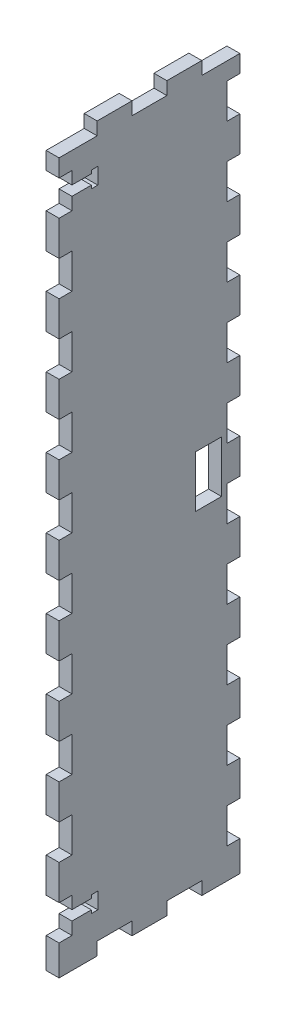
SolidWorks part; units mm, degrees
ref_plane "Front Plane" through (0, 0, 0) normal (0, 0, 1) x (1, 0, 0)
ref_plane "Top Plane" through (0, 0, 0) normal (0, 1, 0) x (1, 0, 0)
ref_plane "Right Plane" through (0, 0, 0) normal (1, 0, 0) x (0, 0, -1)
sketch "Sketch1" plane through (0, 0, 0) normal (1, 0, 0) x (0, 0, -1)
  line L0 (6.35, 355.6) -> (6.35, 349.25) construction
  line L1 (0, 0) -> (88.9, 0) construction
  line L2 (0, 0) -> (0, 6.35) construction
  line L3 (6.35, 355.6) -> (76.2, 355.6) construction
  line L4 (88.9, 0) -> (88.9, 6.35) construction
  line L5 (0, 6.35) -> (88.9, 6.35) construction
  line L6 (6.35, 349.25) -> (88.9, 349.25) construction
  line L7 (82.55, 355.6) -> (82.55, 338.1375) construction
  line L8 (0, 6.35) -> (0, 0)
  line L9 (0, 0) -> (6.35, 0)
  line L10 (6.35, 0) -> (18.7325, 0)
  line L11 (18.7325, 0) -> (18.7325, 6.35)
  line L12 (18.7325, 6.35) -> (35.8775, 6.35)
  line L13 (35.8775, 6.35) -> (35.8775, 0)
  line L14 (35.8775, 0) -> (53.0225, 0)
  line L15 (53.0225, 0) -> (53.0225, 6.35)
  line L16 (53.0225, 6.35) -> (70.1675, 6.35)
  line L17 (70.1675, 6.35) -> (70.1675, 0)
  line L18 (70.1675, 0) -> (82.55, 0)
  line L19 (82.55, 0) -> (88.9, 0)
  line L20 (88.9, 0) -> (88.9, 6.35)
  line L21 (6.35, 12.3825) -> (6.35, 0) construction
  line L22 (0, 0) -> (0, 349.25) construction
  line L23 (0, 6.35) -> (0, 14.9225)
  line L24 (0, 49.2125) -> (6.35, 49.2125)
  line L25 (6.35, 49.2125) -> (6.35, 66.3575)
  line L26 (6.35, 66.3575) -> (0, 66.3575)
  line L27 (0, 66.3575) -> (0, 83.5025)
  line L28 (0, 83.5025) -> (6.35, 83.5025)
  line L29 (6.35, 83.5025) -> (6.35, 100.6475)
  line L30 (6.35, 100.6475) -> (0, 100.6475)
  line L31 (0, 100.6475) -> (0, 117.7925)
  line L32 (0, 117.7925) -> (6.35, 117.7925)
  line L33 (6.35, 117.7925) -> (6.35, 134.9375)
  line L34 (6.35, 134.9375) -> (0, 134.9375)
  line L35 (0, 134.9375) -> (0, 152.0825)
  line L36 (0, 152.0825) -> (6.35, 152.0825)
  line L37 (6.35, 152.0825) -> (6.35, 169.2275)
  line L38 (6.35, 169.2275) -> (0, 169.2275)
  line L39 (0, 169.2275) -> (0, 186.3725)
  line L40 (0, 186.3725) -> (6.35, 186.3725)
  line L41 (6.35, 186.3725) -> (6.35, 203.5175)
  line L42 (6.35, 203.5175) -> (0, 203.5175)
  line L43 (0, 203.5175) -> (0, 220.6625)
  line L44 (0, 220.6625) -> (6.35, 220.6625)
  line L45 (6.35, 220.6625) -> (6.35, 237.8075)
  line L46 (6.35, 237.8075) -> (0, 237.8075)
  line L47 (0, 237.8075) -> (0, 254.9525)
  line L48 (0, 254.9525) -> (6.35, 254.9525)
  line L49 (6.35, 254.9525) -> (6.35, 272.0975)
  line L50 (6.35, 272.0975) -> (0, 272.0975)
  line L51 (0, 272.0975) -> (0, 289.2425)
  line L52 (0, 289.2425) -> (6.35, 289.2425)
  line L53 (6.35, 289.2425) -> (6.35, 306.3875)
  line L54 (6.35, 306.3875) -> (0, 306.3875)
  line L55 (0, 306.3875) -> (0, 323.5325)
  line L56 (0, 323.5325) -> (6.35, 323.5325)
  line L57 (6.35, 323.5325) -> (6.35, 329.692)
  line L58 (6.35, 340.6775) -> (0, 340.6775)
  line L59 (0, 340.6775) -> (0, 349.25)
  line L60 (6.35, 349.25) -> (0, 349.25)
  line L61 (6.35, 334.518) -> (6.35, 340.6775)
  line L62 (6.35, 349.25) -> (18.7325, 349.25)
  line L63 (18.7325, 349.25) -> (18.7325, 355.6)
  line L64 (18.7325, 355.6) -> (35.8775, 355.6)
  line L65 (35.8775, 355.6) -> (35.8775, 349.25)
  line L66 (35.8775, 349.25) -> (53.0225, 349.25)
  line L67 (53.0225, 349.25) -> (53.0225, 355.6)
  line L68 (53.0225, 355.6) -> (70.1675, 355.6)
  line L69 (70.1675, 355.6) -> (70.1675, 349.25)
  line L70 (70.1675, 349.25) -> (88.9, 349.25)
  line L71 (88.9, 6.35) -> (88.9, 14.9225)
  line L72 (88.9, 14.9225) -> (82.55, 14.9225)
  line L73 (82.55, 12.3825) -> (82.55, 0) construction
  line L74 (82.55, 14.9225) -> (82.55, 32.0675)
  line L75 (82.55, 32.0675) -> (88.9, 32.0675)
  line L76 (88.9, 32.0675) -> (88.9, 49.2125)
  line L77 (88.9, 66.3575) -> (88.9, 83.5025)
  line L78 (82.55, 66.3575) -> (88.9, 66.3575)
  line L79 (82.55, 49.2125) -> (82.55, 66.3575)
  line L80 (88.9, 49.2125) -> (82.55, 49.2125)
  line L81 (88.9, 100.6475) -> (88.9, 117.7925)
  line L82 (82.55, 100.6475) -> (88.9, 100.6475)
  line L83 (82.55, 83.5025) -> (82.55, 100.6475)
  line L84 (88.9, 83.5025) -> (82.55, 83.5025)
  line L85 (88.9, 134.9375) -> (88.9, 152.0825)
  line L86 (82.55, 134.9375) -> (88.9, 134.9375)
  line L87 (82.55, 117.7925) -> (82.55, 134.9375)
  line L88 (88.9, 117.7925) -> (82.55, 117.7925)
  line L89 (88.9, 169.2275) -> (88.9, 186.3725)
  line L90 (82.55, 169.2275) -> (88.9, 169.2275)
  line L91 (82.55, 152.0825) -> (82.55, 169.2275)
  line L92 (88.9, 152.0825) -> (82.55, 152.0825)
  line L93 (88.9, 203.5175) -> (88.9, 220.6625)
  line L94 (82.55, 203.5175) -> (88.9, 203.5175)
  line L95 (82.55, 186.3725) -> (82.55, 203.5175)
  line L96 (88.9, 186.3725) -> (82.55, 186.3725)
  line L97 (88.9, 237.8075) -> (88.9, 254.9525)
  line L98 (82.55, 237.8075) -> (88.9, 237.8075)
  line L99 (82.55, 220.6625) -> (82.55, 237.8075)
  line L100 (88.9, 220.6625) -> (82.55, 220.6625)
  line L101 (88.9, 272.0975) -> (88.9, 289.2425)
  line L102 (82.55, 272.0975) -> (88.9, 272.0975)
  line L103 (82.55, 254.9525) -> (82.55, 272.0975)
  line L104 (88.9, 254.9525) -> (82.55, 254.9525)
  line L105 (88.9, 306.3875) -> (88.9, 323.5325)
  line L106 (82.55, 306.3875) -> (88.9, 306.3875)
  line L107 (82.55, 289.2425) -> (82.55, 306.3875)
  line L108 (88.9, 289.2425) -> (82.55, 289.2425)
  line L109 (88.9, 340.6775) -> (88.9, 349.25)
  line L110 (82.55, 340.6775) -> (88.9, 340.6775)
  line L111 (88.9, 6.35) -> (88.9, 0)
  line L112 (82.55, 323.5325) -> (82.55, 340.6775)
  line L113 (0, 46.6725) -> (0, 49.2125) construction
  line L114 (88.9, 323.5325) -> (82.55, 323.5325)
  line L115 (0, 14.9225) -> (6.35, 14.9225)
  line L116 (6.35, 14.9225) -> (6.35, 21.082)
  line L117 (6.35, 32.0675) -> (0, 32.0675)
  line L118 (0, 32.0675) -> (0, 49.2125)
  line L119 (6.35, 332.105) -> (19.05, 332.105) construction
  line L120 (19.05, 328.105) -> (15.875, 328.105)
  line L121 (6.35, 334.518) -> (15.875, 334.518)
  line L122 (15.875, 329.692) -> (15.875, 328.105)
  line L123 (6.35, 329.692) -> (15.875, 329.692)
  line L124 (19.05, 328.105) -> (19.05, 336.105)
  line L125 (19.05, 336.105) -> (15.875, 336.105)
  line L126 (15.875, 334.518) -> (15.875, 336.105)
  line L127 (0, 177.8) -> (88.9237, 177.8) construction
  line L128 (6.35, 25.908) -> (15.875, 25.908)
  line L129 (6.35, 21.082) -> (15.875, 21.082)
  line L130 (19.05, 19.495) -> (15.875, 19.495)
  line L131 (15.875, 21.082) -> (15.875, 19.495)
  line L132 (19.05, 27.495) -> (19.05, 19.495)
  line L133 (19.05, 27.495) -> (15.875, 27.495)
  line L134 (15.875, 25.908) -> (15.875, 27.495)
  line L135 (6.35, 25.908) -> (6.35, 32.0675)
  line L136 (79.8785, 190.5) -> (67.1785, 190.5)
  line L138 (79.8785, 190.5) -> (79.8785, 165.1)
  line L139 (79.8785, 165.1) -> (67.1785, 165.1)
  line L140 (67.1785, 190.5) -> (67.1785, 165.1)
  point P139 (79.8785, 177.8)
  point P140 (67.1785, 177.8)
  dimension "D2" = 10
  dimension "D3" = 6.35
  dimension "D4" = 6.35
  dimension "D5" = 6.35
  dimension "D6" = 6.35
  dimension "D7" = 12.3825
  dimension "D8" = 17.145
  dimension "D9" = 17.145
  dimension "D10" = 12.3825
  dimension "D11" = 8.5725
  dimension "D12" = 10
  dimension "D13" = 4
  dimension "D14" = 3.175
  dimension "D15" = 9.525
  dimension "D16" = 2.413
  dimension "D17" = 6.35
  dimension "D18" = 17.145
  dimension "D19" = 12.3825
  dimension "D20" = 17.145
  dimension "D21" = 17.145
  dimension "D22" = 17.145
  dimension "D23" = 18.7325
  dimension "D24" = 12.7
  dimension "D25" = 12.7
extrude "Boss-Extrude1" add sketch "Sketch1" along normal blind 6.35 contours L111 L107 L103 L95 L83 L78 L70 L69 L68 L67 L66 L65 L64 L63 L62 region at (0, 177.0068, -44.2759)
